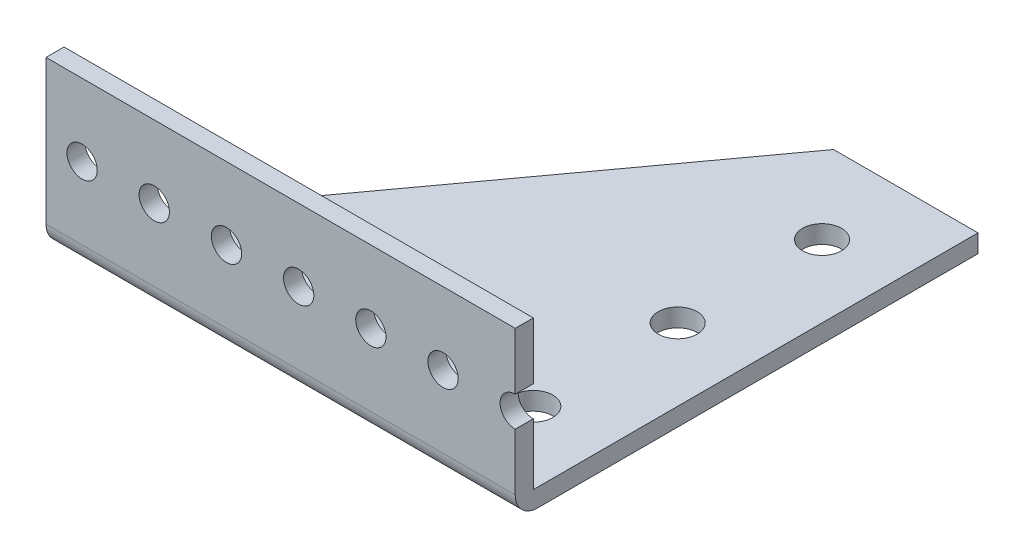
SolidWorks part; units mm, degrees
ref_plane "Front Plane" through (0, 0, 0) normal (0, 0, 1) x (1, 0, 0)
ref_plane "Top Plane" through (0, 0, 0) normal (0, 1, 0) x (1, 0, 0)
ref_plane "Right Plane" through (0, 0, 0) normal (1, 0, 0) x (0, 0, -1)
sketch "Sketch1" plane through (0, 0, 0) normal (0, 1, 0) x (1, 0, 0)
  line L0 (41.275, -40.7035) -> (41.275, 40.7035)
  line L1 (41.275, 40.7035) -> (-41.275, 40.7035)
  line L3 (-41.275, -40.7035) -> (-41.275, 40.7035)
  line L4 (-41.275, -40.7035) -> (41.275, -40.7035)
  line L5 (41.275, 40.7035) -> (-41.275, -40.7035) construction
  line L6 (0, -55) -> (0, 55) construction
  line L7 (-55, 0) -> (55, 0) construction
  point P2 (0, 0)
  dimension "D2" = 81.407
  dimension "D1" = 82.55
extrude "Boss-Extrude1" add sketch "Sketch1" along normal blind 3.175 from offset 34.925 offset against normal yes
sketch "Sketch3" plane through (0, -31.75, 0) normal (0, 1, 0) x (1, 0, 0)
  line L0 (41.275, -40.7035) -> (-41.275, -40.7035)
  line L1 (-41.275, -40.7035) -> (-41.275, -37.5285)
  line L2 (-41.275, -37.5285) -> (41.275, -37.5285)
  line L3 (-41.275, -40.7035) -> (41.275, -40.7035) construction
  line L4 (41.275, -40.7035) -> (41.275, -37.5285)
  line L5 (-41.275, 40.7035) -> (-41.275, -40.7035) construction
  line L6 (41.275, -40.7035) -> (41.275, 40.7035) construction
  dimension "D1" = 3.175
extrude "Boss-Extrude2" add sketch "Sketch3" along normal blind 50.8
hole_wizard "#10 Clearance Hole2" positions "Sketch7" profile "Sketch6" hole size "#10" standard "ANSI Inch" end condition through all
sketch "Sketch7" plane through (0, 0, -40.7035) normal (0, 0, -1) x (-1, 0, 0)
  line L2 (-41.275, -18.288) -> (34.925, -18.288) construction
  line L5 (-41.275, 7.112) -> (34.925, 7.112) construction
  line L8 (41.275, 19.05) -> (41.275, -31.75) construction
  line L9 (-41.275, 19.05) -> (-41.275, -31.75) construction
  line L10 (-41.275, 19.05) -> (41.275, 19.05) construction
  point P56 (22.225, 7.112)
  point P57 (9.525, 7.112)
  point P58 (-3.175, 7.112)
  point P59 (-15.875, 7.112)
  point P61 (-28.575, 7.112)
  point P118 (22.225, -18.288)
  point P119 (9.525, -18.288)
  point P120 (-3.175, -18.288)
  point P121 (-15.875, -18.288)
  point P123 (-28.575, -18.288)
  point P157 (34.925, 7.112)
  point P159 (34.925, -18.288)
  point P185 (-41.275, 7.112)
  point P189 (-41.275, -18.288)
  dimension "D1" = 6.35
  dimension "D2" = 11.938
  dimension "D3" = 12.7
  dimension "D4" = 25.4
  dimension "D5" = 12.7
  dimension "D6" = 12.7
  dimension "D7" = 12.7
  dimension "D8" = 12.7
  dimension "D10" = 12.7
sketch "Sketch6" plane through (-22.225, 7.112, -40.7035) normal (1, 0, 0) x (0, 1, 0)
  line L0 (0, 0) -> (0, 81.407)
  line L1 (0, 81.407) -> (2.667, 81.407)
  line L2 (2.667, 81.407) -> (2.667, 0)
  line L5 (2.667, 0) -> (0, 0)
  line L11 (0, -6.35) -> (0, 107.95) construction
  dimension "Thru Hole Dia." = 5.334
  dimension "Thru Hole Depth" = 81.407
chamfer "Chamfer1" distance 3.175 angle 45 1 edges at (-41.275, 19.05, 39.116)
fillet "Fillet2" radius 3.937 1 edges at (0, -34.925, 40.7035) tangent propagation no
sketch "Sketch9" plane through (0, -34.925, 0) normal (0, -1, 0) x (1, 0, 0)
  line L0 (-41.275, 37.5285) -> (15.875, -40.7035)
  line L1 (-41.275, -40.7035) -> (-41.275, 36.7665) construction
  line L2 (41.275, -40.7035) -> (-41.275, -40.7035) construction
  line L3 (41.275, 36.7665) -> (41.275, -40.7035) construction
  line L4 (15.875, -40.7035) -> (-41.275, -40.7035)
  line L5 (-41.275, -40.7035) -> (-41.275, 37.5285)
  line L6 (-41.275, 40.7035) -> (41.275, 40.7035) construction
  line L7 (28.575, -40.7035) -> (28.575, 36.7665) construction
  line L8 (41.275, 36.7665) -> (-41.275, 36.7665) construction
  line L9 (41.275, 37.5285) -> (-41.275, 37.5285) construction
  circle A0 centre (34.925, 23.9395) radius 3.429 construction
  circle A1 centre (34.925, 11.2395) radius 3.429 construction
  circle A2 centre (34.925, -1.4605) radius 3.429 construction
  circle A3 centre (28.575, 24.8285) radius 3.429
  circle A7 centre (28.575, -0.5715) radius 3.429
  circle A8 centre (28.575, -25.9715) radius 3.429
  dimension "D3" = 6.858
  dimension "D7" = 16.764
  dimension "D9" = 6.858
  dimension "D10" = 12.7
  dimension "D11" = 3
  dimension "D12" = 25.4
  dimension "D1" = 25.4
  dimension "D2" = 0
  dimension "D4" = 12.7
  dimension "D5" = 12.7
  dimension "D6" = 6.35
  dimension "D8" = 12.7
extrude "Cut-Extrude2" cut sketch "Sketch9" against normal through all
sketch "Sketch10" plane through (0, 0, 40.7035) normal (0, 0, 1) x (1, 0, 0)
  line L0 (41.275, -5.588) -> (-41.275, -5.588)
  line L1 (41.275, 4.445) -> (41.275, -15.621) construction
  line L2 (-41.275, 15.875) -> (-41.275, -30.988) construction
  line L3 (-41.275, -5.588) -> (-41.275, 19.05)
  line L4 (-41.275, 19.05) -> (41.275, 19.05)
  line L5 (41.275, 19.05) -> (41.275, -5.588)
extrude "Cut-Extrude3" cut sketch "Sketch10" against normal through all
